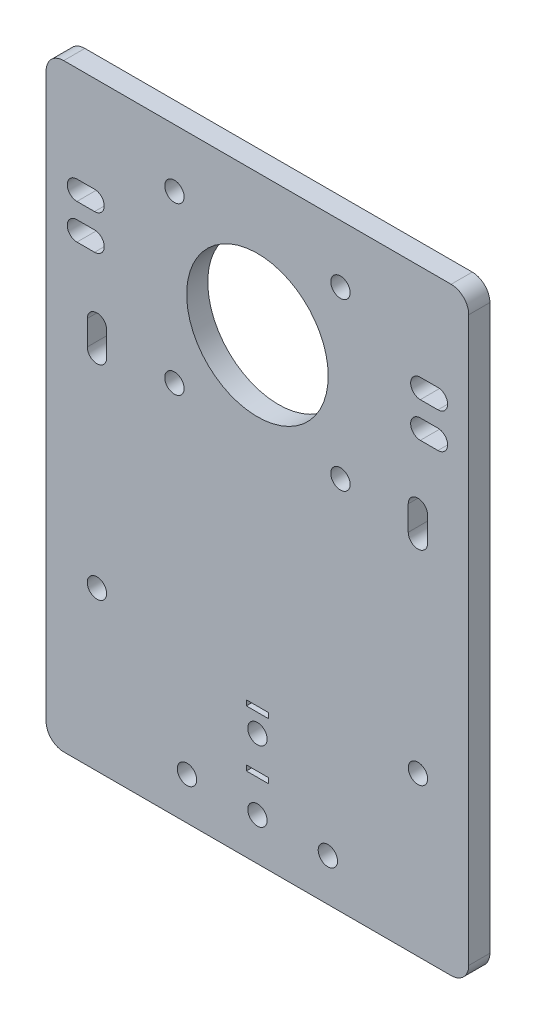
SolidWorks part; units mm, degrees
ref_plane "Front Plane" through (0, 0, 0) normal (0, 0, 1) x (1, 0, 0)
ref_plane "Top Plane" through (0, 0, 0) normal (0, 1, 0) x (1, 0, 0)
ref_plane "Right Plane" through (0, 0, 0) normal (1, 0, 0) x (0, 0, -1)
sketch "Sketch1" plane through (0, 0, 0) normal (0, 0, 1) x (1, 0, 0)
  line L1 (-55, -85) -> (55, -85)
  line L2 (-60, -80) -> (-60, 80)
  line L3 (-55, 85) -> (55, 85)
  line L4 (60, -80) -> (60, 80)
  line L5 (-60, -85) -> (60, 85) construction
  line L6 (-60, 85) -> (60, -85) construction
  arc A0 (-55, -85) -> (-60, -80) centre (-55, -80) cw
  arc A1 (55, -85) -> (60, -80) centre (55, -80) ccw
  arc A2 (55, 85) -> (60, 80) centre (55, 80) cw
  arc A3 (-60, 80) -> (-55, 85) centre (-55, 80) cw
  point P0 (0, 0)
  dimension "D3" = 5
  dimension "D1" = 170
  dimension "D2" = 120
extrude "Boss-Extrude1" add sketch "Sketch1" along normal blind 6
sketch "Sketch3" plane through (0, 0, 6) normal (0, 0, 1) x (1, 0, 0)
  line L0 (55, 85) -> (-55, 85) construction
  circle A0 centre (0, 45) radius 20.1
  point P6 (0, 85)
  dimension "D1" = 40
  dimension "D2" = 40.2
extrude "Cut-Extrude1" cut sketch "Sketch3" against normal blind 6
hole_wizard "M5 Clearance Hole1" positions "Sketch8" profile "Sketch9" hole size "M5" standard "ANSI Metric" end condition through all
sketch "Sketch8" plane through (0, 0, 6) normal (0, 0, 1) x (1, 0, 0)
  circle A0 centre (0, 45) radius 20.1 construction
  point P0 (-23.57, 68.57)
  point P2 (23.57, 68.57)
  point P4 (23.57, 21.43)
  point P6 (-23.57, 21.43)
  dimension "D2" = 23.57
  dimension "D3" = 23.57
  dimension "D4" = 23.57
  dimension "D5" = 23.57
  dimension "D1" = 23.57
sketch "Sketch9" plane through (-23.57, 68.57, 6) normal (1, 0, 0) x (0, -1, 0)
  line L0 (0, 0) -> (0, 6)
  line L1 (0, 6) -> (2.75, 6)
  line L2 (2.75, 6) -> (2.75, 0)
  line L5 (2.75, 0) -> (0, 0)
  line L11 (0, -6.35) -> (0, 107.95) construction
  dimension "Thru Hole Dia." = 5.5
  dimension "Thru Hole Depth" = 6
sketch "Sketch11" plane through (0, 0, 6) normal (0, 0, 1) x (1, 0, 0)
  line L0 (-45.57, 24.93) -> (-45.57, 17.93) construction
  line L1 (-42.82, 24.93) -> (-42.82, 17.93)
  line L2 (-48.32, 24.93) -> (-48.32, 17.93)
  line L5 (0, 63.1141) -> (0, -86.0691) construction
  line L8 (45.57, 24.93) -> (45.57, 17.93) construction
  line L9 (42.82, 24.93) -> (42.82, 17.93)
  line L10 (48.32, 24.93) -> (48.32, 17.93)
  arc A0 (-42.82, 24.93) -> (-48.32, 24.93) centre (-45.57, 24.93) ccw
  arc A1 (-48.32, 17.93) -> (-42.82, 17.93) centre (-45.57, 17.93) ccw
  circle A3 centre (-23.57, 21.43) radius 2.75 construction
  arc A4 (42.82, 24.93) -> (48.32, 24.93) centre (45.57, 24.93) cw
  arc A5 (48.32, 17.93) -> (42.82, 17.93) centre (45.57, 17.93) cw
  point P2 (-45.57, 21.43)
  point P15 (45.57, 21.43)
  dimension "D2" = 2.75
  dimension "D1" = 7
  dimension "D3" = 22
extrude "Cut-Extrude2" cut sketch "Sketch11" against normal blind 6
sketch "Sketch15" plane through (0, 0, 6) normal (0, 0, 1) x (1, 0, 0)
  line L0 (-51.25, 45) -> (-46.25, 45) construction
  line L1 (-51.25, 47.75) -> (-46.25, 47.75)
  line L2 (-51.25, 42.25) -> (-46.25, 42.25)
  line L3 (-51.25, 55) -> (-46.25, 55) construction
  line L4 (-51.25, 57.75) -> (-46.25, 57.75)
  line L5 (-51.25, 52.25) -> (-46.25, 52.25)
  line L6 (-60, 80) -> (-60, -80) construction
  line L8 (55, 85) -> (-55, 85) construction
  line L9 (0, 75.2932) -> (0, -13.323) construction
  line L10 (0, 63.1141) -> (0, -86.0691) construction
  line L11 (51.25, 45) -> (46.25, 45) construction
  line L12 (51.25, 47.75) -> (46.25, 47.75)
  line L13 (51.25, 42.25) -> (46.25, 42.25)
  line L14 (51.25, 55) -> (46.25, 55) construction
  line L15 (51.25, 57.75) -> (46.25, 57.75)
  line L16 (51.25, 52.25) -> (46.25, 52.25)
  arc A0 (-51.25, 47.75) -> (-51.25, 42.25) centre (-51.25, 45) ccw
  arc A1 (-46.25, 42.25) -> (-46.25, 47.75) centre (-46.25, 45) ccw
  arc A2 (-51.25, 57.75) -> (-51.25, 52.25) centre (-51.25, 55) ccw
  arc A3 (-46.25, 52.25) -> (-46.25, 57.75) centre (-46.25, 55) ccw
  arc A5 (51.25, 47.75) -> (51.25, 42.25) centre (51.25, 45) cw
  arc A6 (46.25, 42.25) -> (46.25, 47.75) centre (46.25, 45) cw
  arc A7 (51.25, 57.75) -> (51.25, 52.25) centre (51.25, 55) cw
  arc A8 (46.25, 52.25) -> (46.25, 57.75) centre (46.25, 55) cw
  point P2 (-48.75, 45)
  point P7 (-48.75, 55)
  point P15 (-54, 45)
  point P32 (48.75, 45)
  point P39 (48.75, 55)
  dimension "D1" = 30
  dimension "D2" = 2.75
  dimension "D4" = 5
  dimension "D5" = 6
  dimension "D6" = 10
extrude "Cut-Extrude4" cut sketch "Sketch15" against normal blind 6
hole_wizard "M5 Clearance Hole3" positions "Sketch17" profile "Sketch18" hole size "M5" standard "ANSI Metric" end condition through all
sketch "Sketch17" plane through (0, 0, 6) normal (0, 0, 1) x (1, 0, 0)
  line L1 (-55, -85) -> (55, -85) construction
  line L2 (60, -80) -> (60, 80) construction
  line L3 (-60, 80) -> (-60, -80) construction
  point P0 (-45.57, -39.97)
  point P2 (45.57, -39.97)
  point P4 (20, -73)
  point P6 (0, -73)
  point P8 (-20, -73)
  dimension "D3" = 40
  dimension "D1" = 61.4
  dimension "D2" = 12
  dimension "D4" = 40
sketch "Sketch18" plane through (-45.57, -39.97, 6) normal (1, 0, 0) x (0, -1, 0)
  line L0 (0, 0) -> (0, 6)
  line L1 (0, 6) -> (2.75, 6)
  line L2 (2.75, 6) -> (2.75, 0)
  line L5 (2.75, 0) -> (0, 0)
  line L11 (0, -6.35) -> (0, 107.95) construction
  dimension "Thru Hole Dia." = 5.5
  dimension "Thru Hole Depth" = 6
hole_wizard "M5 Clearance Hole2" positions "Sketch19" profile "Sketch20" hole size "M5" standard "ANSI Metric"
sketch "Sketch19" plane through (0, 0, 0) normal (0, 0, -1) x (-1, 0, 0)
  circle A0 centre (0, -73) radius 2.75 construction
  point P0 (0, -53)
  dimension "D1" = 20
sketch "Sketch20" plane through (0, -53, 0) normal (1, 0, 0) x (0, 1, 0)
  line L0 (0, 0) -> (0, 11.6524)
  line L1 (0, 11.6524) -> (2.75, 10)
  line L2 (2.75, 10) -> (2.75, 0)
  line L5 (2.75, 0) -> (0, 0)
  line L10 (0, 11.6524) -> (-2.75, 10) construction
  line L11 (0, -6.35) -> (0, 107.95) construction
  dimension "Hole Dia." = 5.5
  dimension "Hole Depth" = 10
  dimension "Drill Angle" = 118
sketch "Sketch21" plane through (0, 0, 0) normal (0, 0, -1) x (-1, 0, 0)
  line L1 (-3.15, -46.25) -> (3.15, -46.25)
  line L2 (-3.15, -46.25) -> (-3.15, -47.75)
  line L3 (-3.15, -47.75) -> (3.15, -47.75)
  line L4 (3.15, -46.25) -> (3.15, -47.75)
  line L5 (-3.15, -46.25) -> (3.15, -47.75) construction
  line L6 (-3.15, -47.75) -> (3.15, -46.25) construction
  circle A0 centre (0, -53) radius 2.75 construction
  point P0 (0, -47)
  dimension "D1" = 6.3
  dimension "D2" = 1.5
  dimension "D3" = 6
extrude "Cut-Extrude5" cut sketch "Sketch21" against normal blind 6
sketch "Sketch22" plane through (0, 0, 6) normal (0, 0, 1) x (1, 0, 0)
  line L1 (-3.15, -63.75) -> (3.15, -63.75)
  line L2 (-3.15, -63.75) -> (-3.15, -62.25)
  line L3 (-3.15, -62.25) -> (3.15, -62.25)
  line L4 (3.15, -63.75) -> (3.15, -62.25)
  line L5 (-3.15, -63.75) -> (3.15, -62.25) construction
  line L6 (-3.15, -62.25) -> (3.15, -63.75) construction
  circle A0 centre (0, -53) radius 2.75 construction
  point P0 (0, -63)
  dimension "D1" = 6.3
  dimension "D2" = 1.5
  dimension "D3" = 10
extrude "Cut-Extrude6" cut sketch "Sketch22" against normal blind 10
